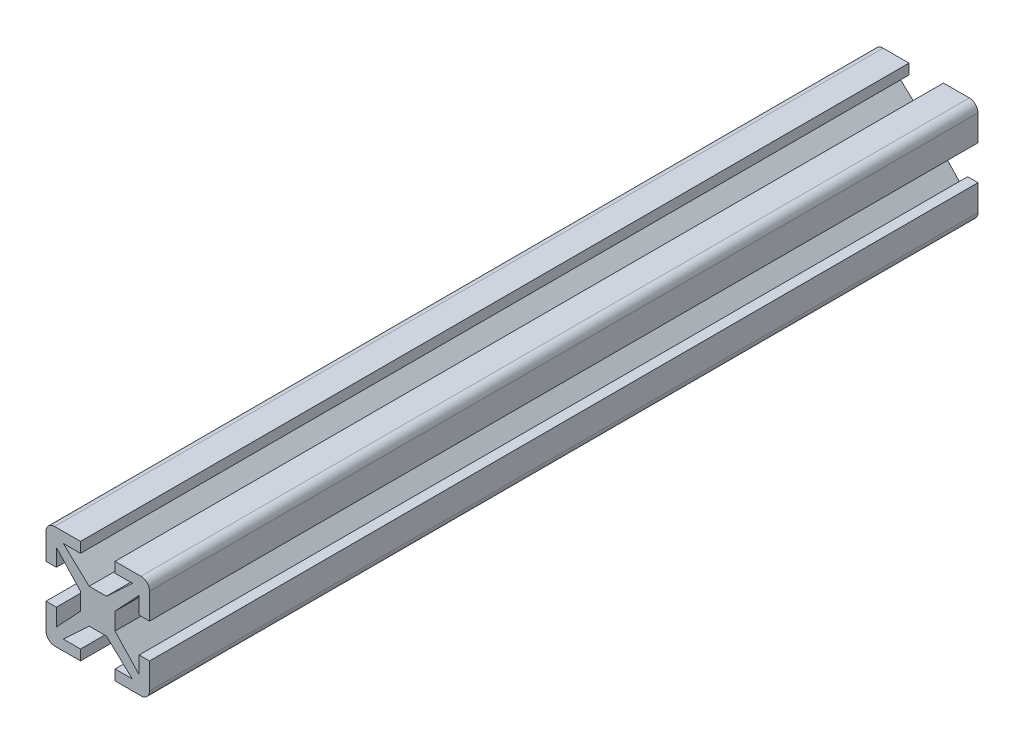
SolidWorks part; units mm, degrees
ref_plane "Plan de face" through (0, 0, 0) normal (0, 0, 1) x (1, 0, 0)
ref_plane "Plan de dessus" through (0, 0, 0) normal (0, 1, 0) x (1, 0, 0)
ref_plane "Plan de droite" through (0, 0, 0) normal (1, 0, 0) x (0, 0, -1)
sketch "Esquisse1" plane through (0, 0, 0) normal (0, 0, 1) x (1, 0, 0)
  line L0 (-6, 5) -> (-6, -5)
  line L1 (-5, 6) -> (5, 6)
  line L2 (-5, -6) -> (5, -6)
  line L3 (6, 5) -> (6, -5)
  line L4 (-5, 5) -> (5, -5) construction
  line L5 (5, 5) -> (-5, -5) construction
  arc A0 (-5, 6) -> (-6, 5) centre (-5, 5) ccw
  arc A1 (5, 6) -> (6, 5) centre (5, 5) cw
  arc A2 (6, -5) -> (5, -6) centre (5, -5) cw
  arc A3 (-5, -6) -> (-6, -5) centre (-5, -5) cw
  point P12 (0, 0)
  dimension "D1" = 1
  dimension "D2" = 1
  dimension "D4" = 1
  dimension "D3" = 12
extrude "Extrusion1" add sketch "Esquisse1" along normal mid plane 96
sketch "Esquisse3" plane through (0, 0, 48) normal (0, 0, 1) x (1, 0, 0)
  line L0 (6, 2) -> (4.8, 2)
  line L2 (4.8, 2) -> (4.8, 4)
  line L3 (2, 1) -> (2, -1)
  line L4 (4.8, -4) -> (4.8, -2)
  line L5 (4.8, -2) -> (6, -2)
  line L6 (6, -5) -> (6, 5) construction
  line L7 (4.8, 4) -> (2, 1)
  line L8 (6, 2) -> (6, -2)
  line L9 (4.8, -4) -> (2, -1)
  point P4 (6, 0)
  point P10 (6, 0)
  dimension "D1" = 4
  dimension "D2" = 1.2
  dimension "D3" = 4
  dimension "D4" = 2
  dimension "D5" = 2
extrude "Enlèv. mat.-Extru.1" cut sketch "Esquisse3" against normal through all
ref_axis "Axe1" through (0, 0, -1) along (0, 0, 1)
pattern_circular "Répétition circulaire1" count 4 every 90 about axis through (0, 0, -1) along (0, 0, 1) of "Enlèv. mat.-Extru.1"
